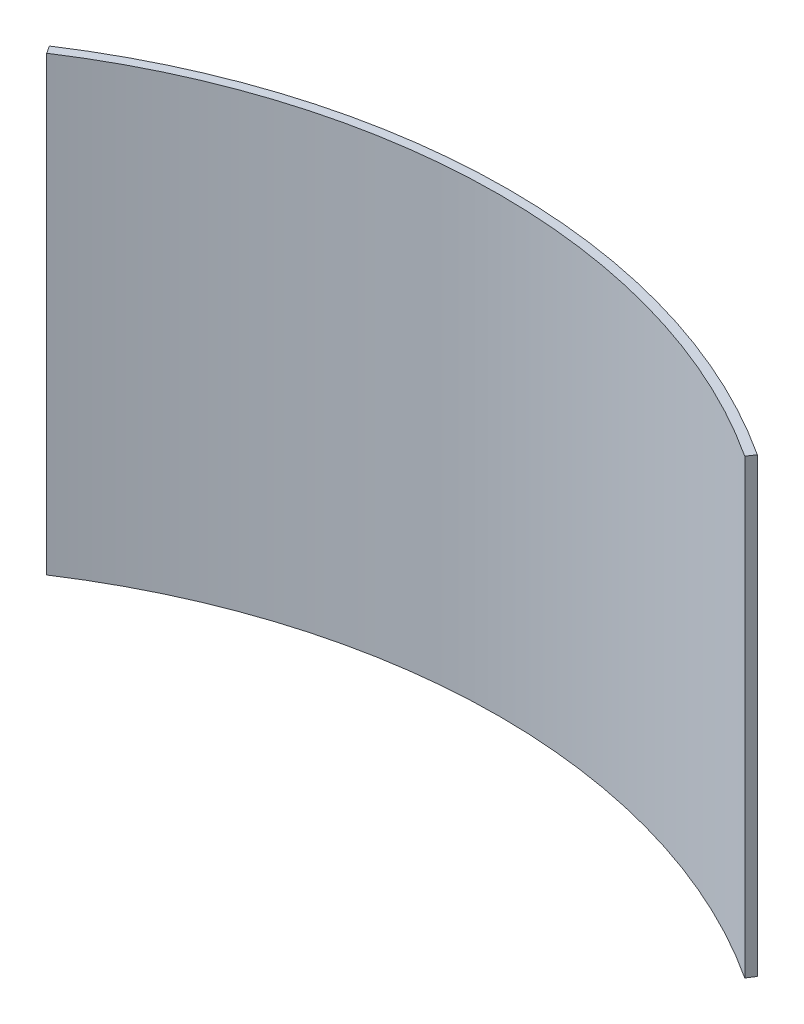
SolidWorks part; units mm, degrees
ref_plane "Спереди" through (0, 0, 0) normal (0, 0, 1) x (1, 0, 0)
ref_plane "Сверху" through (0, 0, 0) normal (0, 1, 0) x (1, 0, 0)
ref_plane "Справа" through (0, 0, 0) normal (1, 0, 0) x (0, 0, -1)
sketch "Эскиз1" plane through (0, 0, 0) normal (0, 1, 0) x (1, 0, 0)
  line L0 (0, 57.5) -> (223.2588, 57.5) construction
  line L1 (92.5, 92.5) -> (236.2741, 92.5) construction
  arc A0 (14.6418, 57.5) -> (249.6418, 57.5) centre (132.1418, -122.2321) cw
  dimension "D1" = 35
  dimension "D2" = 235
extrude "Вытянуть-Тонкостенный1" add sketch "Эскиз1" along normal blind 150 thin thin type one direction wall 3
